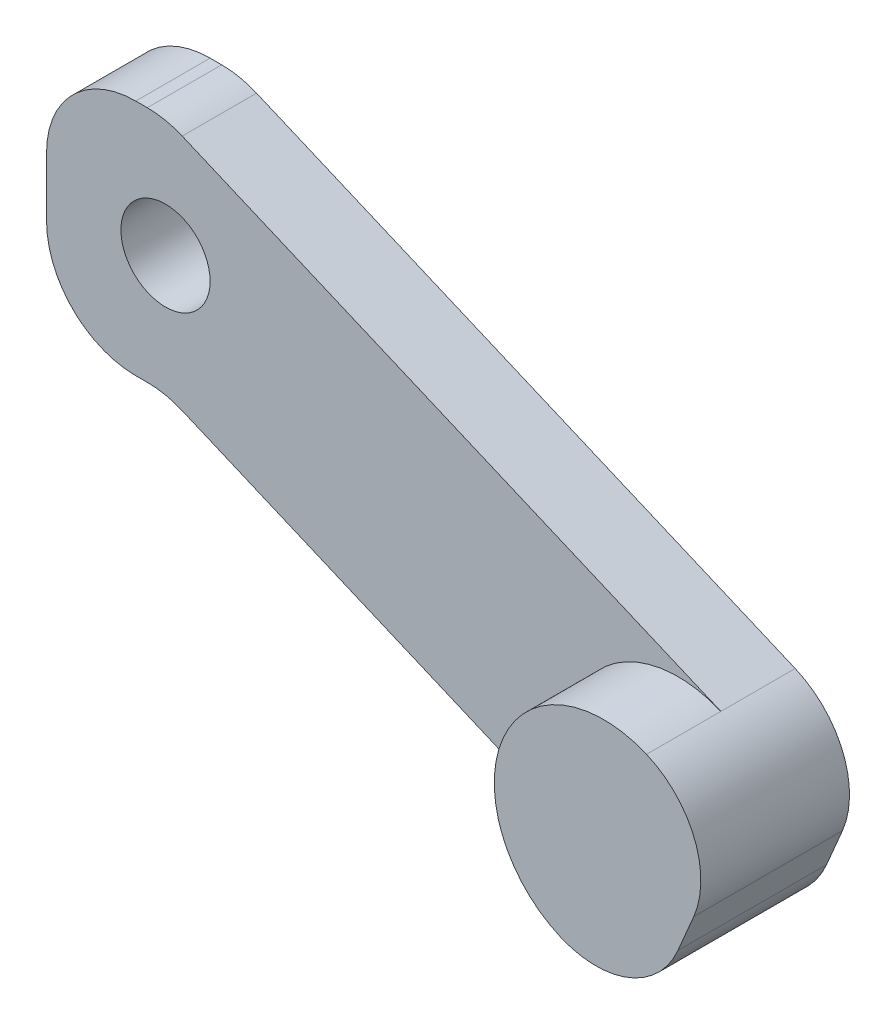
SolidWorks part; units mm, degrees
ref_plane "Plano frontal" through (0, 0, 0) normal (0, 0, 1) x (1, 0, 0)
ref_plane "Plano superior" through (0, 0, 0) normal (0, 1, 0) x (1, 0, 0)
ref_plane "Plano direito" through (0, 0, 0) normal (1, 0, 0) x (0, 0, -1)
sketch "Esboço1" plane through (0, 0, 0) normal (0, 0, 1) x (1, 0, 0)
  line L0 (-8, -8) -> (-8, 8)
  line L5 (-8, 8) -> (0, 8)
  line L6 (0, 8) -> (42.8798, -10.2239)
  line L7 (42.8798, -10.2239) -> (37.1202, -23.7761)
  line L8 (37.1202, -23.7761) -> (0, -8)
  line L9 (0, -8) -> (-8, -8)
  line L10 (-17.8615, 0) -> (30.3176, 0) construction
  circle A0 centre (0, 0) radius 3
  point P0 (0, 0)
  point P14 (40, -17)
  dimension "D3" = 6
  dimension "D1" = 8
  dimension "D2" = 8
  dimension "D4" = 17
  dimension "D5" = 40
extrude "Ressalto-extrusão1" add sketch "Esboço1" along normal blind 5 contours L5 L6 L7 L8 L9 L0 | A0
fillet "Filete1" radius 6 6 edges at (0, -8, 2.5) (-8, -8, 2.5) (-8, 8, 2.5) (0, 8, 2.5) (42.8798, -10.2239, 2.5) (37.1202, -23.7761, 2.5)
sketch "Esboço2" plane through (0, 0, 5) normal (0, 0, 1) x (1, 0, 0)
  line L3 (39.467, -18.2541) -> (40.533, -15.7459)
  line L4 (39.467, -18.2541) -> (40.533, -15.7459)
  arc A4 (37.3578, -7.8771) -> (35.7183, -7.3957) centre (34.478, -14.6532) ccw
  arc A5 (35.7183, -7.3957) -> (31.5982, -21.4292) centre (34.478, -14.6532) ccw
  arc A6 (31.5982, -21.4292) -> (39.467, -18.2541) centre (33.945, -15.9072) ccw
  arc A7 (40.533, -15.7459) -> (37.3578, -7.8771) centre (35.011, -13.3991) ccw
  arc A8 (31.5982, -21.4292) -> (39.467, -18.2541) centre (33.945, -15.9072) ccw
  arc A9 (40.533, -15.7459) -> (37.3578, -7.8771) centre (35.011, -13.3991) ccw
  dimension "D1" = 0
extrude "Ressalto-extrusão2" add sketch "Esboço2" along normal blind 5
